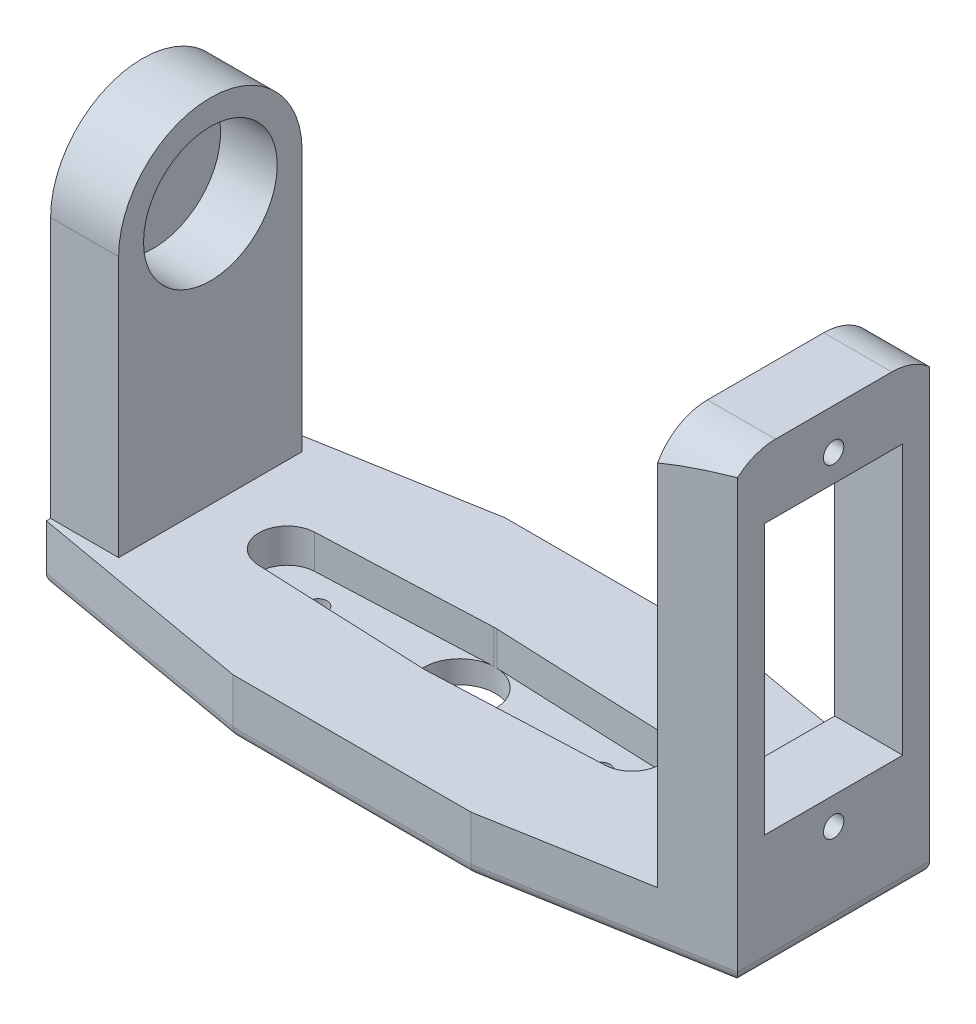
SolidWorks part; units mm, degrees
ref_plane "前视基准面" through (0, 0, 0) normal (0, 0, 1) x (1, 0, 0)
ref_plane "上视基准面" through (0, 0, 0) normal (0, 1, 0) x (1, 0, 0)
ref_plane "右视基准面" through (0, 0, 0) normal (1, 0, 0) x (0, 0, -1)
sketch "草图1" plane through (0, 0, 0) normal (0, 1, 0) x (1, 0, 0)
  line L0 (0, 0) -> (2.5, 0) construction
  line L1 (33, -12) -> (-28, -12)
  line L2 (33, -12) -> (33, 12)
  line L3 (33, 12) -> (-28, 12)
  line L4 (-28, -12) -> (-28, 12)
  line L5 (33, -12) -> (-28, 12) construction
  line L6 (33, 12) -> (-28, -12) construction
  point P0 (0, 0)
  dimension "D1" = 28
  dimension "D2" = 33
  dimension "D3" = 24
extrude "凸台-拉伸1" add sketch "草图1" along normal blind 5
sketch "草图2" plane through (-28, 0, 0) normal (-1, 0, 0) x (0, 0, 1)
  line L0 (-12, 5) -> (12, 5) construction
  line L1 (8.0991, 36.0991) -> (-8.0991, 36.0991)
  line L2 (8.0991, 36.0991) -> (8.0991, 5)
  line L3 (8.0991, 5) -> (-8.0991, 5)
  line L4 (-8.0991, 36.0991) -> (-8.0991, 5)
  line L5 (8.0991, 36.0991) -> (-8.0991, 5) construction
  line L6 (8.0991, 5) -> (-8.0991, 36.0991) construction
  line L7 (0, 20.5496) -> (0, 5) construction
  circle A0 centre (0, 28) radius 5.9
  circle A1 centre (0, 28) radius 8.0991 construction
  point P0 (0, 20.5496)
  dimension "D2" = 11.8
  dimension "D1" = 23
extrude "凸台-拉伸2" add sketch "草图2" against normal blind 6
sketch "草图8" plane through (-28, 0, 0) normal (-1, 0, 0) x (0, 0, 1)
  circle A1 centre (0, 28) radius 5.9 construction
  circle A2 centre (0, 28) radius 5.9
extrude "凸台-拉伸4" add sketch "草图8" against normal blind 1
fillet "圆角1" 2 edges at (-25, 36.0991, -8.0991) (-25, 36.0991, 8.0991) type full round first side face at (-25, 20.5496, -8.0991) second side face at (-25, 20.5496, 8.0991) middle face at (-25, 36.0991, 0)
sketch "草图3" plane through (33, 0, 0) normal (1, 0, 0) x (0, 0, -1)
  line L0 (0, 22.2) -> (18.2252, 22.2) construction
  line L1 (10.134, 40.0752) -> (-10.134, 40.0752)
  line L2 (10.134, 40.0752) -> (10.134, 5)
  line L3 (10.134, 5) -> (-10.134, 5)
  line L4 (-10.134, 40.0752) -> (-10.134, 5)
  line L5 (10.134, 40.0752) -> (-10.134, 5) construction
  line L6 (10.134, 5) -> (-10.134, 40.0752) construction
  line L7 (0, 22.2) -> (0, 0) construction
  line L8 (6.1, 34.1) -> (-6.1, 34.1)
  line L9 (6.1, 34.1) -> (6.1, 10.3)
  line L10 (6.1, 10.3) -> (-6.1, 10.3)
  line L11 (-6.1, 34.1) -> (-6.1, 10.3)
  line L12 (6.1, 34.1) -> (-6.1, 10.3) construction
  line L13 (6.1, 10.3) -> (-6.1, 34.1) construction
  line L17 (-12, 5) -> (12, 5) construction
  circle A0 centre (0, 28) radius 5.9 construction
  circle A1 centre (0, 28) radius 5.9 construction
  circle A2 centre (0, 7.9) radius 0.9
  circle A3 centre (0, 36.5) radius 0.9
  circle A4 centre (0, 28) radius 6.1 construction
  point P0 (0, 22.5376)
  point P7 (0, 22.2)
  dimension "D5" = 1.8
  dimension "D1" = 23.8
  dimension "D2" = 12.2
  dimension "D4" = 14.3
extrude "凸台-拉伸3" add sketch "草图3" against normal blind 6
fillet "圆角2" radius 5 2 edges at (30, 40.0752, 10.134) (30, 40.0752, -10.134)
chamfer "倒角1" distance 20 angle 10 4 edges at (33, 2.5, -12) (33, 2.5, 12) (-28, 2.5, 12) (-28, 2.5, -12) first distance on face at (2.5, 2.5, -12) first distance on face at (2.5, 2.5, 12)
fillet "圆角4" radius 1 8 edges at (-18, 0, -10.2367) (-28, 0, 0) (-18, 0, 10.2367) (2.5, 0, 12) (23, 0, 10.2367) (33, 0, 0) (23, 0, -10.2367) (2.5, 0, -12)
sketch "草图4" plane through (-24, 5, 6) normal (0, -1, 0) x (-1, 0, 0)
  line L0 (-24, 6) -> (-8.7944, 6) construction
  line L1 (-8.6961, 3.7021) -> (-23.8739, 3.0527) construction
  line L2 (-23.8739, 8.9473) -> (-8.6961, 8.2979) construction
  line L3 (-23.8653, 9.1471) -> (-8.6876, 8.4977)
  line L4 (-8.6876, 3.5023) -> (-23.8653, 2.8529)
  arc A0 (-23.8739, 8.9473) -> (-23.8739, 3.0527) centre (-24, 6) ccw construction
  arc A1 (-8.6961, 3.7021) -> (-8.6961, 8.2979) centre (-8.7944, 6) ccw construction
  arc A2 (-8.6876, 3.5023) -> (-8.6876, 8.4977) centre (-8.7944, 6) ccw
  arc A3 (-23.8653, 9.1471) -> (-23.8653, 2.8529) centre (-24, 6) ccw
  dimension "D1" = 5.9
  dimension "D2" = 4.6
  dimension "D3" = 4.9
  dimension "D5" = 0.2
extrude "切除-拉伸1" cut sketch "草图4" along normal blind 3
mirror "镜向1" about plane through (0, 0, 0) normal (1, 0, 0) of "切除-拉伸1"
sketch "草图5" plane through (0, 2, 0) normal (0, 1, 0) x (1, 0, 0)
  line L0 (-12.5, 0) -> (0, 0) construction
  line L1 (0, 0) -> (0, 5.837) construction
  arc A1 (-0.1347, -3.1471) -> (0.1347, -3.1471) centre (0, 0) ccw construction
  arc A2 (0.1347, 3.1471) -> (-0.1347, 3.1471) centre (0, 0) ccw construction
  arc A3 (-0.1347, -3.1471) -> (0.1347, -3.1471) centre (0, 0) ccw construction
  arc A4 (0.1347, 3.1471) -> (-0.1347, 3.1471) centre (0, 0) ccw construction
  circle A5 centre (0, 0) radius 3.15
  circle A6 centre (-12.5, 0) radius 0.8
  circle A7 centre (12.5, 0) radius 0.8
  dimension "D2" = 1.6
  dimension "D1" = 12.5
extrude "切除-拉伸2" cut sketch "草图5" against normal blind 2.4
sketch "草图10" plane through (0, 5, 0) normal (0, 1, 0) x (1, 0, 0)
  line L0 (-11.9016, -10.3725) -> (11.9016, -10.3725) construction
  line L1 (0, 0) -> (0, -10.3725) construction
  text T0 "V1.7" font "思源黑体" height in points 18
extrude "凸台-拉伸5" [suppressed] add sketch "草图10" along normal blind 0.6
